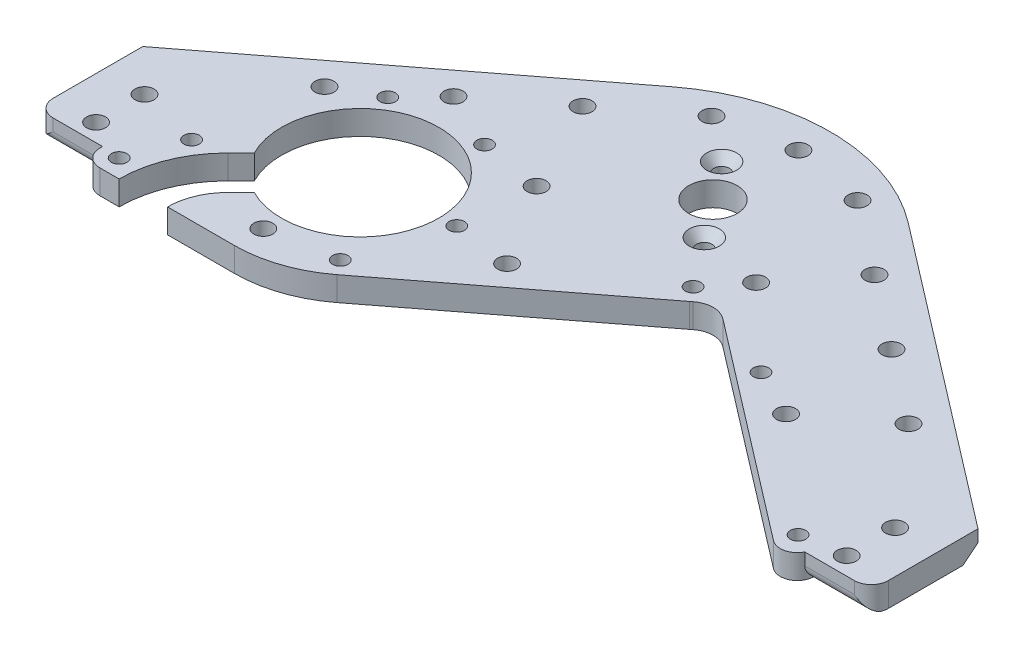
SolidWorks part; units mm, degrees
material "Alum Plate"
ref_plane "Front Plane" through (0, 0, 0) normal (0, 0, 1) x (1, 0, 0)
ref_plane "Top Plane" through (0, 0, 0) normal (0, 1, 0) x (1, 0, 0)
ref_plane "Right Plane" through (0, 0, 0) normal (1, 0, 0) x (0, 0, -1)
sketch "Top Layout" plane through (0, 0, 0) normal (0, 1, 0) x (1, 0, 0)
  line L0 (-114.046, -123.825) -> (-104.775, -123.825) construction
  line L1 (-104.775, -142.875) -> (-101.6, -142.875)
  line L2 (-104.775, -142.875) -> (-104.775, -104.775)
  line L3 (-104.775, -104.775) -> (-101.6, -104.775)
  line L4 (-101.6, -142.875) -> (-101.6, -104.775)
  line L5 (-104.775, -142.875) -> (-101.6, -104.775) construction
  line L6 (-104.775, -104.775) -> (-101.6, -142.875) construction
  line L7 (-19.05, -105.8164) -> (-101.6, -105.8164)
  line L8 (-19.05, -105.8164) -> (-19.05, -141.8336)
  line L9 (-19.05, -141.8336) -> (-101.6, -141.8336)
  line L10 (-101.6, -105.8164) -> (-101.6, -141.8336)
  line L11 (-19.05, -105.8164) -> (-101.6, -141.8336) construction
  line L12 (-19.05, -141.8336) -> (-101.6, -105.8164) construction
  line L13 (-133.096, -85.725) -> (-114.046, -85.725)
  line L14 (-133.096, -85.725) -> (-133.096, -161.925)
  line L15 (-133.096, -161.925) -> (-114.046, -161.925)
  line L16 (-114.046, -85.725) -> (-114.046, -161.925)
  line L17 (-133.096, -85.725) -> (-114.046, -161.925) construction
  line L18 (-133.096, -161.925) -> (-114.046, -85.725) construction
  line L19 (-104.775, -123.825) -> (0, -123.825) construction
  line L20 (0, -123.825) -> (0, 0) construction
  line L21 (-52.3528, -40.1717) -> (0, 0) construction
  line L22 (-70.6449, -16.3328) -> (-18.2922, 23.8388)
  line L23 (-34.0606, -64.0105) -> (18.2922, -23.8388)
  line L24 (-30.9251, 40.3023) -> (-122.2248, -29.7544)
  line L25 (-153.9748, -53.975) -> (-153.9748, -123.825)
  line L26 (-109.5248, -162.052) -> (109.5248, -162.052)
  line L27 (0, -162.052) -> (0, -123.825) construction
  line L28 (-109.5248, -162.052) -> (-109.5248, -20.0093) construction
  line L29 (-104.775, -142.875) -> (-104.775, -152.527)
  line L30 (-104.775, -152.527) -> (104.775, -152.527)
  line L31 (104.775, -104.775) -> (101.6, -104.775)
  line L32 (-144.4498, -73.025) -> (-109.5248, -73.025)
  line L33 (-144.4498, -73.025) -> (-144.4498, -123.825)
  line L34 (-144.4498, -123.825) -> (-109.5248, -123.825) construction
  line L35 (-109.5248, -73.025) -> (-109.5248, -162.052)
  line L36 (-144.4498, -73.025) -> (-109.5248, -123.825) construction
  line L37 (-144.4498, -123.825) -> (-109.5248, -73.025) construction
  line L38 (101.6, -142.875) -> (101.6, -104.775)
  line L39 (104.775, -142.875) -> (101.6, -142.875)
  line L40 (104.775, -142.875) -> (104.775, -104.775)
  line L41 (104.775, -142.875) -> (104.775, -152.527)
  line L42 (109.5248, -162.052) -> (109.5248, -20.0093) construction
  line L43 (30.9251, 40.3023) -> (122.2248, -29.7544)
  line L45 (19.05, -141.8336) -> (101.6, -141.8336)
  line L46 (101.6, -105.8164) -> (101.6, -141.8336)
  line L47 (19.05, -105.8164) -> (101.6, -105.8164)
  line L48 (19.05, -105.8164) -> (19.05, -141.8336)
  line L49 (133.096, -161.925) -> (114.046, -161.925)
  line L50 (114.046, -85.725) -> (114.046, -161.925)
  line L51 (133.096, -85.725) -> (114.046, -85.725)
  line L52 (133.096, -85.725) -> (133.096, -161.925)
  line L53 (144.4498, -123.825) -> (109.5248, -123.825) construction
  line L54 (109.5248, -73.025) -> (109.5248, -162.052)
  line L55 (144.4498, -73.025) -> (109.5248, -73.025)
  line L56 (144.4498, -73.025) -> (144.4498, -123.825)
  line L57 (-109.5248, -123.825) -> (-109.5248, -162.052) construction
  line L62 (-153.9748, -53.975) -> (-122.2248, -53.975)
  line L63 (-122.2248, -53.975) -> (-122.2248, -29.7544)
  line L64 (-144.4498, -123.825) -> (-153.9748, -123.825)
  line L65 (153.9748, -53.975) -> (153.9748, -123.825)
  line L66 (109.5248, -123.825) -> (109.5248, -162.052) construction
  line L67 (144.4498, -123.825) -> (153.9748, -123.825)
  line L68 (122.2248, -29.7544) -> (122.2248, -53.975)
  line L73 (-104.775, -104.775) -> (-104.775, -16.3647) construction
  line L74 (-95.25, -162.052) -> (-95.25, -9.0559) construction
  line L75 (-109.5248, -162.052) -> (-109.5248, -123.825) construction
  line L76 (109.5248, -162.052) -> (109.5248, -123.825) construction
  line L77 (122.2248, -53.975) -> (153.9748, -53.975)
  line L83 (104.775, -155.5496) -> (-104.775, -155.5496) construction
  line L88 (95.25, -162.052) -> (95.25, -9.0559) construction
  line L89 (104.775, -104.775) -> (104.775, -16.3647) construction
  line L92 (-104.775, -152.527) -> (-104.775, -162.052) construction
  line L93 (-14.605, -76.327) -> (14.605, -76.327)
  line L94 (-14.605, -76.327) -> (-14.605, -152.527)
  line L95 (-14.605, -152.527) -> (14.605, -152.527)
  line L96 (14.605, -76.327) -> (14.605, -152.527)
  line L97 (-14.605, -76.327) -> (14.605, -152.527) construction
  line L98 (-14.605, -152.527) -> (14.605, -76.327) construction
  line L99 (104.775, -152.527) -> (104.775, -162.052) construction
  line L100 (-19.05, -105.8164) -> (0, -105.8164) construction
  line L107 (0, -105.8164) -> (19.05, -105.8164) construction
  line L108 (104.775, -123.825) -> (114.046, -123.825) construction
  circle A0 centre (0, 0) radius 114.3
  circle A1 centre (0, 0) radius 6.35
  circle A2 centre (-52.3528, -40.1717) radius 17.8
  circle A3 centre (0, 0) radius 30.0482
  circle A4 centre (-52.3528, -40.1717) radius 30.0482
  arc A5 (-30.9251, 40.3023) -> (30.9251, 40.3023) centre (0, 0) cw
  point P2 (-103.1875, -123.825)
  point P7 (-60.325, -123.825)
  point P12 (-123.571, -123.825)
  point P30 (-126.9873, -98.425)
  point P35 (0, -114.427)
  point P53 (0, -152.527)
  dimension "D1" = 35.6
  dimension "D2" = 12.7
  dimension "D3" = 228.6
  dimension "D11" = 60.0964
  dimension "D12" = 50.8
  dimension "D14" = 52.5
  dimension "D4" = 3.175
  dimension "D5" = 19.05
  dimension "D6" = 76.2
  dimension "D7" = 82.55
  dimension "D8" = 38.1
  dimension "D9" = 104.775
  dimension "D10" = 18.0086
  dimension "D13" = 9.525
  dimension "D15" = 4.7498
  dimension "D16" = 9.525
  dimension "D17" = 9.652
  dimension "D18" = 50.8
  dimension "D19" = 12.446
  dimension "D20" = 65.9892
  dimension "D21" = 19.05
  dimension "D22" = 34.925
  dimension "D23" = 123.825
  dimension "D24" = 12.7
  dimension "D25" = 9.525
  dimension "D26" = 29.21
  dimension "D27" = 76.2
  dimension "D28" = 3.0226
sketch "Side Layout" plane through (0, 0, 0) normal (1, 0, 0) x (0, 0, -1)
  line L0 (0, -38.1) -> (0, 33.7344) construction
  line L1 (-114.3, -20.955) -> (114.3, -20.955)
  line L2 (-114.3, -20.955) -> (-114.3, -33.655)
  line L3 (-114.3, -33.655) -> (114.3, -33.655)
  line L4 (114.3, -20.955) -> (114.3, -33.655)
  line L5 (-114.3, -20.955) -> (114.3, -33.655) construction
  line L6 (-114.3, -33.655) -> (114.3, -20.955) construction
  line L7 (-9.525, -32.9406) -> (9.525, -32.9406)
  line L8 (-9.525, -32.9406) -> (-9.525, -38.1)
  line L9 (-9.525, -38.1) -> (9.525, -38.1)
  line L10 (9.525, -32.9406) -> (9.525, -38.1)
  line L11 (-9.525, -32.9406) -> (9.525, -38.1) construction
  line L12 (-9.525, -38.1) -> (9.525, -32.9406) construction
  line L13 (-11.9126, -29.3338) -> (11.9126, -29.3338)
  line L14 (-11.9126, -29.3338) -> (-11.9126, -32.9406)
  line L15 (-11.9126, -32.9406) -> (11.9126, -32.9406)
  line L16 (11.9126, -29.3338) -> (11.9126, -32.9406)
  line L17 (-11.9126, -29.3338) -> (11.9126, -32.9406) construction
  line L18 (-11.9126, -32.9406) -> (11.9126, -29.3338) construction
  line L19 (-6.35, -32.9406) -> (6.35, -32.9406)
  line L20 (-6.35, -32.9406) -> (-6.35, 33.7344)
  line L21 (-6.35, 33.7344) -> (6.35, 33.7344)
  line L22 (6.35, -32.9406) -> (6.35, 33.7344)
  line L23 (-6.35, -32.9406) -> (6.35, 33.7344) construction
  line L24 (-6.35, 33.7344) -> (6.35, -32.9406) construction
  line L25 (-162.052, 0) -> (-123.825, 0) construction
  line L26 (114.3, -33.655) -> (114.3, 0) construction
  line L27 (-142.875, 19.05) -> (-104.775, 19.05)
  line L28 (-40.1717, -9.525) -> (-40.1717, 5.4) construction
  line L29 (-142.875, 19.05) -> (-142.875, -19.05)
  line L30 (-142.875, -19.05) -> (-104.775, -19.05)
  line L31 (-104.775, 19.05) -> (-104.775, -19.05)
  line L32 (-142.875, 19.05) -> (-104.775, -19.05) construction
  line L33 (-142.875, -19.05) -> (-104.775, 19.05) construction
  line L34 (-130.175, -38.1) -> (-117.9516, -38.1) construction
  line L35 (-57.9717, -14.6) -> (-22.3717, -14.6)
  line L36 (-30.0482, -2.794) -> (30.0482, -2.794)
  line L37 (-30.0482, -2.794) -> (-30.0482, -20.955)
  line L38 (-30.0482, -20.955) -> (30.0482, -20.955)
  line L39 (30.0482, -2.794) -> (30.0482, -20.955)
  line L40 (-30.0482, -2.794) -> (30.0482, -20.955) construction
  line L41 (-30.0482, -20.955) -> (30.0482, -2.794) construction
  line L42 (-30.0482, -2.794) -> (-30.0482, 0) construction
  line L43 (-123.825, 0) -> (0, 0) construction
  line L44 (-57.9717, -14.6) -> (-57.9717, 25.4)
  line L45 (-57.9717, 25.4) -> (-22.3717, 25.4)
  line L46 (-22.3717, -14.6) -> (-22.3717, 25.4)
  line L47 (-19.05, 0) -> (19.05, 0)
  line L48 (-19.05, 0) -> (-19.05, -1.9812)
  line L49 (-19.05, -1.9812) -> (19.05, -1.9812)
  line L50 (19.05, 0) -> (19.05, -1.9812)
  line L51 (-19.05, 0) -> (19.05, -1.9812) construction
  line L52 (-19.05, -1.9812) -> (19.05, 0) construction
  line L53 (-70.2199, -3.175) -> (-10.1235, -3.175)
  line L54 (-70.2199, -3.175) -> (-70.2199, -15.875)
  line L55 (-70.2199, -15.875) -> (-10.1235, -15.875)
  line L56 (-10.1235, -3.175) -> (-10.1235, -15.875)
  line L57 (-70.2199, -3.175) -> (-10.1235, -15.875) construction
  line L58 (-70.2199, -15.875) -> (-10.1235, -3.175) construction
  line L59 (-40.1717, -9.525) -> (-40.1717, 0) construction
  line L60 (-57.9717, -14.6) -> (-22.3717, 25.4) construction
  line L61 (-57.9717, 25.4) -> (-22.3717, -14.6) construction
  line L62 (-22.3717, 0) -> (-57.9717, 0) construction
  line L63 (-137.8162, 0) -> (-123.825, -13.9912) construction
  line L64 (-139.065, 15.24) -> (-108.585, 15.24) construction
  line L65 (-139.065, 15.24) -> (-139.065, -15.24) construction
  line L66 (-139.065, -15.24) -> (-108.585, -15.24) construction
  line L67 (-108.585, 15.24) -> (-108.585, -15.24) construction
  line L68 (-139.065, 15.24) -> (-108.585, -15.24) construction
  line L69 (-139.065, -15.24) -> (-108.585, 15.24) construction
  line L70 (-137.8162, 0) -> (-123.825, 13.9912) construction
  line L71 (-123.825, -13.9912) -> (-109.8338, 0) construction
  line L72 (-123.825, 13.9912) -> (-109.8338, 0) construction
  line L73 (-137.8162, 0) -> (-109.8338, 0) construction
  line L74 (-123.825, -13.9912) -> (-123.825, 13.9912) construction
  line L75 (-6.35, 17.8594) -> (6.35, 17.8594)
  line L76 (114.3, 0) -> (-114.3, 0) construction
  line L77 (-22.3717, 19.05) -> (-6.35, 19.05) construction
  line L78 (-123.825, 38.1) -> (-97.9206, 38.1) construction
  line L79 (-19.05, -3.5814) -> (19.05, -3.5814)
  line L80 (-19.05, -3.5814) -> (-19.05, -1.9812)
  line L81 (-19.05, -1.9812) -> (19.05, -1.9812)
  line L82 (19.05, -3.5814) -> (19.05, -1.9812)
  line L83 (-19.05, -3.5814) -> (19.05, -1.9812) construction
  line L84 (-19.05, -1.9812) -> (19.05, -3.5814) construction
  line L85 (-8.7376, -16.7608) -> (8.7376, -16.7608)
  line L86 (-8.7376, -16.7608) -> (-8.7376, -29.3338)
  line L87 (-8.7376, -29.3338) -> (8.7376, -29.3338)
  line L88 (8.7376, -16.7608) -> (8.7376, -29.3338)
  line L89 (-8.7376, -16.7608) -> (8.7376, -29.3338) construction
  line L90 (-8.7376, -29.3338) -> (8.7376, -16.7608) construction
  line L91 (-8.7376, -3.5814) -> (8.7376, -3.5814)
  line L92 (-8.7376, -3.5814) -> (-8.7376, -16.1544)
  line L93 (-8.7376, -16.1544) -> (8.7376, -16.1544)
  line L94 (8.7376, -3.5814) -> (8.7376, -16.1544)
  line L95 (-8.7376, -3.5814) -> (8.7376, -16.1544) construction
  line L96 (-8.7376, -16.1544) -> (8.7376, -3.5814) construction
  circle A0 centre (-123.825, 0) radius 18.0086
  circle A1 centre (-123.825, 0) radius 38.1
  circle A2 centre (-139.065, 15.24) radius 1.905
  circle A3 centre (-108.585, 15.24) radius 1.905
  circle A4 centre (-108.585, -15.24) radius 1.905
  circle A5 centre (-139.065, -15.24) radius 1.905
  circle A6 centre (-137.8162, 0) radius 1.6002
  circle A7 centre (-123.825, 13.9912) radius 1.6002
  circle A8 centre (-109.8338, 0) radius 1.6002
  circle A9 centre (-123.825, -13.9912) radius 1.6002
  point P0 (0, -27.305)
  point P6 (0, -31.1372)
  point P7 (0, -35.5203)
  point P21 (0, 0.3969)
  point P32 (0, -11.8745)
  point P43 (0, -0.9906)
  point P55 (-40.1717, -9.525)
  point P72 (-40.1717, 5.4)
  point P88 (0, -23.0473)
  point P93 (0, -2.7813)
  point P102 (0, -9.8679)
  dimension "D17" = 3.81
  dimension "D18" = 3.2004
  dimension "D1" = 12.7
  dimension "D2" = 5.1594
  dimension "D3" = 19.05
  dimension "D4" = 3.6068
  dimension "D5" = 23.8252
  dimension "D6" = 12.7
  dimension "D7" = 18.161
  dimension "D8" = 1.9812
  dimension "D9" = 12.7
  dimension "D10" = 40
  dimension "D11" = 25.4
  dimension "D12" = 50.8
  dimension "D13" = 41.275
  dimension "D14" = 30.48
  dimension "D15" = 4.445
  dimension "D16" = 19.7866
  dimension "D19" = 15.875
  dimension "D20" = 6.35
  dimension "D21" = 38.1
  dimension "D22" = 1.6002
  dimension "D23" = 38.1
  dimension "D24" = 17.4752
  dimension "D25" = 12.573
ref_plane "Plane1" through (0, 25.4, 0) normal (0, 1, 0) x (1, 0, 0)
sketch "Sketch3" plane through (0, 25.4, 0) normal (0, 1, 0) x (1, 0, 0)
  line L0 (-104.775, -36.3747) -> (-30.9251, 20.2924)
  line L1 (-104.775, -104.775) -> (-104.775, -16.3647) construction
  line L2 (0, -200130.175) -> (0, 199882.0484) construction
  line L3 (-30.9251, 40.3023) -> (-122.2248, -29.7544) construction
  line L5 (-104.775, -36.3747) -> (-104.775, -77.6497)
  line L6 (-92.075, -77.6497) -> (-104.775, -77.6497)
  line L7 (30.9251, 20.2924) -> (104.775, -36.3747)
  line L8 (104.775, -77.6497) -> (92.075, -77.6497)
  line L9 (104.775, -36.3747) -> (104.775, -77.6497)
  line L11 (104.775, -104.775) -> (104.775, -16.3647) construction
  line L12 (30.9251, 40.3023) -> (122.2248, -29.7544) construction
  line L13 (92.075, -74.6536) -> (24.1423, -22.5271)
  line L14 (-32.2514, -66.3682) -> (20.1013, -26.1965)
  line L15 (-30.9251, 20.2924) -> (0, 44.022)
  line L16 (0, 44.022) -> (30.9251, 20.2924)
  line L17 (-92.075, -77.6497) -> (-92.075, -73.1917)
  line L19 (-92.075, -73.1917) -> (-52.3528, -73.1917)
  line L20 (92.075, -74.6536) -> (92.075, -77.6497)
  circle A1 centre (-52.3528, -40.1717) radius 20.6375
  circle A2 centre (0, 0) radius 6.35
  circle A3 centre (0, 0) radius 6.35 construction
  arc A4 (-52.3528, -73.1917) -> (-32.2514, -66.3682) centre (-52.3528, -40.1717) ccw
  arc A5 (20.1013, -26.1965) -> (24.1423, -22.5271) centre (0, 0) ccw
  arc A6 (30.9251, 20.2924) -> (-30.9251, 20.2924) centre (0, -20.01) ccw construction
  point P28 (0, 44.022)
  dimension "D1" = 33.02
  dimension "D5" = 50.8
  dimension "D7" = 41.275
  dimension "D2" = 41.275
  dimension "D3" = 34.925
  dimension "D4" = 12.7
  dimension "D6" = 38.1
extrude "Boss-Extrude1" add sketch "Sketch3" against normal blind 6.35
ref_plane "Plane3" through (-104.775, 0, 0) normal (-1, 0, 0) x (0, 0, 1)
sketch "Sketch6" plane through (-104.775, 0, 0) normal (-1, 0, 0) x (0, 0, 1)
  line L0 (162.052, -25.4) -> (162.052, 25.4)
  line L1 (162.052, 25.4) -> (77.6497, 25.4)
  line L2 (36.3747, 25.4) -> (77.6497, 25.4) construction
  line L3 (147.7645, 11.1125) -> (162.052, 11.1125) construction
  line L4 (162.052, 0) -> (71.2997, 0) construction
  line L5 (77.6497, 25.4) -> (77.6497, 19.05)
  line L6 (77.6497, 19.05) -> (36.3747, 19.05)
  line L7 (36.3747, 19.05) -> (36.3747, 6.35)
  line L8 (36.3747, 6.35) -> (71.2997, 6.35)
  line L10 (99.6315, -3.175) -> (99.6315, 11.1125) construction
  line L11 (71.2997, -25.4) -> (162.052, -25.4)
  line L13 (71.2997, 6.35) -> (71.2997, -25.4)
  line L14 (152.527, -25.4) -> (152.527, 25.4) construction
  line L15 (99.6315, 11.1125) -> (99.6315, 25.4) construction
  line L16 (147.7645, 11.1125) -> (147.7645, 25.4) construction
  line L17 (94.869, -7.9375) -> (104.394, -7.9375) construction
  line L18 (94.869, -7.9375) -> (94.869, 25.4) construction
  line L19 (94.869, 25.4) -> (104.394, 25.4) construction
  line L20 (104.394, -7.9375) -> (104.394, 25.4) construction
  line L21 (94.869, -7.9375) -> (104.394, 25.4) construction
  line L22 (94.869, 25.4) -> (104.394, -7.9375) construction
  line L23 (147.7645, 11.1125) -> (147.7645, -3.175) construction
  line L24 (104.394, -7.9375) -> (123.825, -7.9375) construction
  line L25 (143.002, -7.9375) -> (152.527, -7.9375) construction
  line L26 (143.002, -7.9375) -> (143.002, 25.4) construction
  line L27 (143.002, 25.4) -> (152.527, 25.4) construction
  line L28 (152.527, -7.9375) -> (152.527, 25.4) construction
  line L29 (143.002, -7.9375) -> (152.527, 25.4) construction
  line L30 (143.002, 25.4) -> (152.527, -7.9375) construction
  line L31 (123.825, -7.9375) -> (152.527, -7.9375) construction
  line L32 (104.775, 19.05) -> (104.775, -19.05) construction
  line L34 (155.702, -25.4) -> (155.702, 25.4) construction
  circle A0 centre (109.8338, 0) radius 1.6002 construction
  circle A1 centre (123.825, 13.9912) radius 1.6002 construction
  circle A2 centre (137.8162, 0) radius 1.6002 construction
  circle A3 centre (123.825, -13.9912) radius 1.6002 construction
  circle A4 centre (109.8338, 0) radius 1.6002 construction
  circle A5 centre (123.825, 13.9912) radius 1.6002 construction
  circle A6 centre (137.8162, 0) radius 1.6002 construction
  circle A7 centre (123.825, -13.9912) radius 1.6002 construction
  circle A8 centre (123.825, 0) radius 18.0086 construction
  circle A9 centre (123.825, 0) radius 18.0086 construction
  circle A10 centre (123.825, 0) radius 9.525
  circle A11 centre (108.585, -15.24) radius 1.905 construction
  circle A12 centre (108.585, 15.24) radius 1.905 construction
  circle A13 centre (139.065, 15.24) radius 1.905 construction
  circle A14 centre (139.065, -15.24) radius 1.905 construction
  circle A15 centre (108.585, -15.24) radius 1.905
  circle A16 centre (108.585, 15.24) radius 1.905
  circle A17 centre (139.065, 15.24) radius 1.905
  circle A18 centre (139.065, -15.24) radius 1.905
  circle A19 centre (147.7645, 11.1125) radius 2.5527
  circle A26 centre (99.6315, 11.1125) radius 2.5527
  circle A27 centre (99.6315, -3.175) radius 2.5527
  circle A28 centre (147.7645, -3.175) radius 2.5527
  point P29 (0, 0)
  point P55 (99.6315, 8.7312)
  point P61 (147.7645, 8.7312)
  dimension "D4" = 19.05
  dimension "D7" = 5.1054
  dimension "D1" = 6.35
  dimension "D2" = 12.7
  dimension "D3" = 25.4
  dimension "D5" = 6.35
  dimension "D6" = 3.175
  dimension "D8" = 0.381
  dimension "D9" = 14.2875
  dimension "D10" = 9.525
  dimension "D12" = 33.3375
sketch "Sketch12" [suppressed] plane through (0, 19.05, 0) normal (0, 1, 0) x (1, 0, 0)
  line L0 (-104.775, -77.6497) -> (-104.775, -36.3747)
  line L1 (-104.775, -36.3747) -> (-92.075, -36.3747)
  line L3 (-92.075, -36.3747) -> (-92.075, -77.6497)
  line L5 (-92.075, -77.6497) -> (-104.775, -77.6497)
  line L6 (-98.425, -77.6497) -> (-98.425, -63.3622) construction
  line L7 (-98.425, -63.3622) -> (-98.425, -50.6622) construction
  line L8 (-98.425, -50.6622) -> (-98.425, -36.3747) construction
  line L10 (-98.425, -36.3747) -> (-104.775, -36.3747) construction
  circle A0 centre (-98.425, -63.3622) radius 2.5527
  circle A1 centre (-98.425, -50.6622) radius 2.5527
  dimension "D2" = 5.1054
  dimension "D1" = 12.7
  dimension "D3" = 12.7
sketch "Sketch8" plane through (0, 25.4, 0) normal (0, 1, 0) x (1, 0, 0)
  line L0 (-109.5248, -162.052) -> (-109.5248, -20.0093) construction
  line L1 (-104.775, -77.6497) -> (-109.5248, -77.6497)
  line L2 (-104.775, -77.6497) -> (-104.775, -36.3747)
  line L3 (-104.775, -36.3747) -> (-109.5248, -36.3747)
  line L4 (-109.5248, -77.6497) -> (-109.5248, -36.3747)
  line L5 (-104.775, -77.6497) -> (-109.5248, -36.3747) construction
  line L6 (-104.775, -36.3747) -> (-109.5248, -77.6497) construction
  line L7 (104.775, -77.6497) -> (109.5248, -77.6497)
  line L8 (104.775, -77.6497) -> (104.775, -36.3747)
  line L9 (104.775, -36.3747) -> (109.5248, -36.3747)
  line L10 (109.5248, -77.6497) -> (109.5248, -36.3747)
  line L11 (104.775, -77.6497) -> (109.5248, -36.3747) construction
  line L12 (104.775, -36.3747) -> (109.5248, -77.6497) construction
  point P4 (-107.1499, -57.0122)
  point P10 (107.1499, -57.0122)
extrude "Boss-Extrude4" add sketch "Sketch8" against normal through all
sketch "Sketch9" plane through (0, 25.4, 0) normal (0, 1, 0) x (1, 0, 0)
  line L0 (7.4916, -9.7632) -> (0, 0) construction
  line L1 (0, 0) -> (-7.4916, 9.7632) construction
  line L2 (0, 44.022) -> (-104.775, -36.3747) construction
  circle A0 centre (-7.4916, 9.7632) radius 2.032
  circle A1 centre (7.4916, -9.7632) radius 2.032
  dimension "D2" = 4.064
  dimension "D1" = 24.6126
extrude "Collar Holes" cut sketch "Sketch9" against normal through all
sketch "Sketch10" plane through (0, 25.4, 0) normal (0, 1, 0) x (1, 0, 0)
  line L0 (0, 33.4567) -> (0, 30.79) construction
  line L1 (-5.1026, 40.1066) -> (0, 33.4567) construction
  line L2 (0, 33.4567) -> (5.1026, 40.1066) construction
  line L3 (0, 44.022) -> (-104.775, -36.3747) construction
  line L4 (104.775, -36.3747) -> (0, 44.022) construction
  circle A0 centre (0, 33.4567) radius 4.7625 construction
  circle A1 centre (0, 33.4567) radius 2.0193
  arc A3 (30.9251, 20.2924) -> (-30.9251, 20.2924) centre (0, -20.01) ccw construction
  dimension "D2" = 9.525
  dimension "D3" = 4.0386
  dimension "D1" = 8.382
extrude "Spacer Holes" cut sketch "Sketch10" against normal through all
pattern_linear "Spacer Hole Pattern" count 5 spacing 24.13 along (-0.7934, 0, 0.6088) of "Spacer Holes"
mirror "Spacer Hole Mirror" about plane through (0, 0, 0) normal (1, 0, 0) of "Spacer Hole Pattern"
sketch "Sketch16" plane through (0, 25.4, 0) normal (0, 1, 0) x (1, 0, 0)
  line L0 (-109.5248, -50.6622) -> (-98.425, -50.6622) construction
  line L1 (-109.5248, -36.3747) -> (-109.5248, -77.6497) construction
  line L2 (-98.425, -50.6622) -> (-98.425, -63.3622) construction
  line L3 (-98.425, -63.3622) -> (-109.5248, -63.3622) construction
  line L4 (-98.425, -63.3622) -> (-98.425, -77.6497) construction
  line L5 (-109.5248, -77.6497) -> (-92.075, -77.6497) construction
  line L6 (-98.425, -50.6622) -> (-98.425, -36.3747) construction
  line L7 (-104.775, -36.3747) -> (-109.5248, -36.3747) construction
  line L8 (-104.775, -36.3747) -> (-104.775, -77.6497) construction
  line L9 (0, 0) -> (0, 30.79) construction
  line L10 (104.775, -36.3747) -> (104.775, -77.6497) construction
  circle A0 centre (-98.425, -50.6622) radius 2.0193
  circle A1 centre (-98.425, -63.3622) radius 2.0193
  circle A4 centre (98.425, -63.3622) radius 2.0193
  circle A5 centre (98.425, -50.6622) radius 2.0193
  arc A6 (30.9251, 20.2924) -> (-30.9251, 20.2924) centre (0, -20.01) ccw construction
  dimension "D1" = 4.0386
  dimension "D2" = 12.7
  dimension "D3" = 6.35
extrude "Custom Nutstrip Holes" cut sketch "Sketch16" against normal through all
sketch "Sketch36" plane through (0, 25.4, 0) normal (0, 1, 0) x (1, 0, 0)
  line L0 (-52.3528, -65.5717) -> (-12.44, -41.5615) construction
  line L1 (-12.44, -41.5615) -> (24.5129, -13.2066) construction
  line L2 (24.5129, -13.2066) -> (58.2939, -39.1277) construction
  line L3 (-32.2514, -66.3682) -> (20.1013, -26.1965) construction
  line L4 (24.1423, -22.5271) -> (92.075, -74.6536) construction
  line L5 (-12.44, -41.5615) -> (-7.8012, -47.6069) construction
  line L6 (58.2939, -39.1277) -> (53.6552, -45.1731) construction
  line L7 (-52.3528, -65.5717) -> (-52.3528, -40.1717) construction
  line L8 (58.2939, -39.1277) -> (92.075, -65.0488) construction
  line L9 (92.075, -65.0488) -> (92.075, -77.6497) construction
  line L10 (-52.3528, -40.1717) -> (-26.1764, -20.0858) construction
  line L11 (-26.1764, -20.0858) -> (0, 0) construction
  line L12 (92.075, -74.6536) -> (92.075, -77.6497) construction
  circle A0 centre (-52.3528, -65.5717) radius 2.0193
  circle A1 centre (58.2939, -39.1277) radius 2.0193
  circle A2 centre (24.5129, -13.2066) radius 2.0193
  circle A3 centre (-12.44, -41.5615) radius 2.0193
  circle A4 centre (-76.5745, -25.3009) radius 2.0193 construction
  circle A5 centre (-52.3528, -65.5717) radius 4.7625 construction
  circle A6 centre (-12.44, -41.5615) radius 4.7625 construction
  circle A7 centre (24.5129, -13.2066) radius 4.7625 construction
  circle A8 centre (58.2939, -39.1277) radius 4.7625 construction
  arc A9 (-52.3528, -73.1917) -> (-32.2514, -66.3682) centre (-52.3528, -40.1717) ccw construction
  circle A10 centre (-26.1764, -20.0858) radius 2.0193
  dimension "D1" = 9.525
  dimension "D2" = 25.4
  dimension "D3" = 7.62
extrude "Aux Spacer Holes" cut sketch "Sketch36" against normal through all
sketch "Sketch38" [suppressed] plane through (-104.775, 0, 0) normal (-1, 0, 0) x (0, 0, 1)
  line L1 (152.527, -7.9375) -> (143.002, -7.9375)
  line L2 (152.527, -7.9375) -> (152.527, 25.4)
  line L3 (152.527, 25.4) -> (143.002, 25.4)
  line L4 (143.002, -7.9375) -> (143.002, 25.4)
  line L5 (152.527, -7.9375) -> (143.002, 25.4) construction
  line L6 (152.527, 25.4) -> (143.002, -7.9375) construction
  point P4 (147.7645, 8.7312)
extrude "Cut-Extrude16" [suppressed] cut sketch "Sketch38" against normal blind 9.525
sketch "Sketch46" [suppressed] plane through (-104.775, 0, 0) normal (-1, 0, 0) x (0, 0, 1)
  line L0 (142.875, 19.05) -> (104.775, -19.05) construction
  line L1 (104.14, 19.685) -> (143.51, 19.685)
  line L2 (104.14, 19.685) -> (104.14, -19.685)
  line L3 (104.14, -19.685) -> (143.51, -19.685)
  line L4 (143.51, 19.685) -> (143.51, -19.685)
  line L5 (104.14, 19.685) -> (143.51, -19.685) construction
  line L6 (104.14, -19.685) -> (143.51, 19.685) construction
  point P0 (123.825, 0)
  dimension "D1" = 39.37
extrude "Cut-Extrude21" [suppressed] cut sketch "Sketch46" against normal blind 6.985
ref_plane "Plane5" through (0, 0, 152.527) normal (0, 0, 1) x (1, 0, 0)
sketch "Sketch41" plane through (0, 0, 152.527) normal (0, 0, 1) x (1, 0, 0)
  line L0 (-104.775, -7.9375) -> (-104.775, 25.4) construction
  line L1 (-104.775, -7.9375) -> (-104.775, 12.7)
  line L2 (-104.775, -7.9375) -> (104.775, -7.9375)
  line L3 (104.775, -7.9375) -> (104.775, 12.7)
  line L4 (104.775, 25.4) -> (-104.775, 25.4)
  line L5 (0, -7.9375) -> (0, 25.4) construction
  line L6 (-104.775, 3.9624) -> (-100.0125, 3.9624) construction
  line L7 (-100.0125, 3.9624) -> (-100.0125, 25.4) construction
  line L8 (104.775, 3.9624) -> (100.0125, 3.9624) construction
  line L9 (100.0125, 3.9624) -> (100.0125, 25.4) construction
  line L10 (19.05, 20.6375) -> (23.8252, 20.6375) construction
  line L11 (19.05, 15.875) -> (78.5876, 15.875) construction
  line L12 (19.05, 15.875) -> (19.05, 25.4) construction
  line L13 (19.05, 25.4) -> (78.5876, 25.4) construction
  line L14 (78.5876, 15.875) -> (78.5876, 25.4) construction
  line L15 (19.05, 15.875) -> (78.5876, 25.4) construction
  line L16 (19.05, 25.4) -> (78.5876, 15.875) construction
  line L17 (23.8252, 20.6375) -> (38.1127, 20.6375) construction
  line L18 (38.1127, 20.6375) -> (52.4002, 20.6375) construction
  line L19 (52.4002, 20.6375) -> (66.6877, 20.6375) construction
  line L20 (-104.775, 25.4) -> (-112.395, 25.4)
  line L21 (-112.395, 25.4) -> (-112.395, 3.175)
  line L22 (-112.395, 3.175) -> (-109.5248, 3.175)
  line L23 (-109.5248, 3.175) -> (-109.5248, 12.7)
  line L24 (-109.5248, 12.7) -> (-104.775, 12.7)
  line L25 (-104.775, 12.7) -> (-104.775, 25.4) construction
  line L26 (104.775, 25.4) -> (112.395, 25.4)
  line L27 (112.395, 25.4) -> (112.395, 3.175)
  line L28 (112.395, 3.175) -> (109.5248, 3.175)
  line L29 (109.5248, 3.175) -> (109.5248, 12.7)
  line L30 (109.5248, 12.7) -> (104.775, 12.7)
  line L31 (104.775, 12.7) -> (104.775, 25.4) construction
  line L32 (-100.0125, 3.9624) -> (-87.3125, 3.9624) construction
  line L33 (-63.5, -1.5875) -> (0, -1.5875) construction
  line L34 (0, -1.5875) -> (63.5, -1.5875) construction
  line L35 (63.5, -1.5875) -> (63.5, -7.9375) construction
  circle A0 centre (-100.0125, 3.9624) radius 2.5527
  circle A1 centre (100.0125, 3.9624) radius 2.5527
  circle A2 centre (23.8252, 20.6375) radius 2.5527
  circle A3 centre (38.1127, 20.6375) radius 2.5527
  circle A4 centre (52.4002, 20.6375) radius 2.5527
  circle A5 centre (66.6877, 20.6375) radius 2.5527
  circle A6 centre (-66.6877, 20.6375) radius 2.5527
  circle A7 centre (-52.4002, 20.6375) radius 2.5527
  circle A8 centre (-38.1127, 20.6375) radius 2.5527
  circle A9 centre (-23.8252, 20.6375) radius 2.5527
  circle A10 centre (-87.3125, 3.9624) radius 2.5527
  circle A11 centre (87.3125, 3.9624) radius 2.5527
  circle A12 centre (-63.5, -1.5875) radius 2.5527
  circle A13 centre (63.5, -1.5875) radius 2.5527
  point P14 (48.8188, 20.6375)
  dimension "D3" = 5.1054
  dimension "D7" = 5.1054
  dimension "D1" = 21.4376
  dimension "D2" = 4.7625
  dimension "D4" = 9.525
  dimension "D5" = 59.5376
  dimension "D6" = 4.7752
  dimension "D8" = 14.2875
  dimension "D9" = 7.62
  dimension "D10" = 4.7498
  dimension "D11" = 12.7
  dimension "D12" = 9.525
  dimension "D13" = 19.05
  dimension "D14" = 12.7
  dimension "D15" = 6.35
  dimension "D16" = 63.5
sketch "Sketch43" [suppressed] plane through (-109.5248, 0, 0) normal (-1, 0, 0) x (0, 0, 1)
  line L1 (152.527, 12.7) -> (155.702, 12.7)
  line L2 (152.527, 12.7) -> (152.527, 25.4)
  line L3 (152.527, 25.4) -> (155.702, 25.4)
  line L4 (155.702, 12.7) -> (155.702, 25.4)
  line L5 (152.527, 12.7) -> (155.702, 25.4) construction
  line L6 (152.527, 25.4) -> (155.702, 12.7) construction
  line L7 (162.052, 25.4) -> (77.6497, 25.4) construction
  point P4 (154.1145, 19.05)
  dimension "D1" = 3.175
sketch "Sketch44" plane through (0, 25.4, 0) normal (0, 1, 0) x (1, 0, 0)
  line L0 (73.8315, -147.7645) -> (73.8315, -152.527) construction
  line L1 (92.075, -74.6536) -> (92.075, -77.6497) construction
  line L2 (-92.075, -77.6497) -> (-92.075, -73.1917) construction
  line L3 (0, -123.825) -> (0, 0) construction
  line L4 (-92.075, -73.1917) -> (-52.3528, -73.1917) construction
  line L5 (-104.775, -104.775) -> (-104.775, -16.3647) construction
  line L6 (-32.2514, -66.3682) -> (20.1013, -26.1965) construction
  line L21 (-104.775, -68.1247) -> (-104.775, -152.527)
  line L22 (-104.775, -152.527) -> (104.775, -152.527)
  line L23 (104.775, -152.527) -> (104.775, -68.1247)
  line L34 (-104.775, -99.6315) -> (-100.0125, -99.6315) construction
  line L35 (-104.775, -147.7645) -> (-100.0125, -147.7645) construction
  line L36 (0, -152.527) -> (0, -35.6178) construction
  line L38 (30.969, -147.7645) -> (45.2565, -147.7645) construction
  line L39 (45.2565, -147.7645) -> (59.544, -147.7645) construction
  line L40 (59.544, -147.7645) -> (73.8315, -147.7645) construction
  line L41 (23.8252, -152.527) -> (30.969, -152.527) construction
  line L42 (104.775, -152.527) -> (-104.775, -152.527) construction
  line L43 (30.969, -152.527) -> (38.1127, -152.527) construction
  line L44 (30.969, -152.527) -> (30.969, -147.7645) construction
  line L45 (-92.075, -77.6497) -> (-104.775, -77.6497) construction
  line L48 (-35.1507, -62.5899) -> (-8.9743, -42.504) construction
  line L49 (-8.9743, -42.504) -> (17.2021, -22.4182) construction
  line L50 (45.5313, -32.9364) -> (87.3125, -64.9962) construction
  line L51 (92.075, -74.6536) -> (24.1423, -22.5271) construction
  line L52 (104.775, -77.6497) -> (92.075, -77.6497) construction
  line L79 (-104.775, -68.1247) -> (-92.075, -68.1247)
  line L80 (-92.075, -68.1247) -> (-92.075, -63.6667)
  line L85 (21.8118, -8.7328) -> (92.075, -62.6476)
  line L86 (-38.0499, -58.8115) -> (14.3028, -18.6398)
  line L87 (-92.075, -63.6667) -> (-52.3528, -63.6667)
  line L88 (92.075, -62.6476) -> (92.075, -68.1247)
  line L89 (92.075, -68.1247) -> (104.775, -68.1247)
  circle A0 centre (-73.8315, -147.7645) radius 2.5527
  circle A1 centre (-59.544, -147.7645) radius 2.5527
  circle A2 centre (-45.2565, -147.7645) radius 2.5527
  circle A3 centre (-30.969, -147.7645) radius 2.5527
  circle A17 centre (-100.0125, -99.6315) radius 2.5527
  circle A18 centre (-100.0125, -147.7645) radius 2.5527
  circle A19 centre (100.0125, -147.7645) radius 2.5527
  circle A20 centre (100.0125, -99.6315) radius 2.5527
  circle A21 centre (30.969, -147.7645) radius 2.5527
  circle A22 centre (45.2565, -147.7645) radius 2.5527
  circle A23 centre (59.544, -147.7645) radius 2.5527
  circle A24 centre (73.8315, -147.7645) radius 2.5527
  circle A25 centre (-87.3125, -68.4292) radius 4.7625 construction
  circle A26 centre (-35.1507, -62.5899) radius 4.7625 construction
  circle A27 centre (-8.9743, -42.504) radius 4.7625 construction
  circle A28 centre (17.2021, -22.4182) radius 4.7625 construction
  circle A29 centre (45.5313, -32.9364) radius 4.7625 construction
  circle A30 centre (87.3125, -64.9962) radius 4.7625 construction
  circle A32 centre (-87.3125, -68.4292) radius 2.5527
  circle A33 centre (-35.1507, -62.5899) radius 2.5527
  circle A34 centre (-8.9743, -42.504) radius 2.5527 construction
  circle A35 centre (17.2021, -22.4182) radius 2.5527
  circle A36 centre (45.5313, -32.9364) radius 2.5527
  circle A37 centre (87.3125, -64.9962) radius 2.5527
  circle A38 centre (-97.155, -85.2697) radius 7.62 construction
  circle A39 centre (97.155, -85.2697) radius 7.62 construction
  circle A40 centre (24.5121, -32.4156) radius 7.62 construction
  arc A41 (20.1013, -26.1965) -> (24.1423, -22.5271) centre (0, 0) ccw construction
  circle A42 centre (-97.155, -85.2697) radius 2.5527
  circle A43 centre (24.5121, -32.4156) radius 2.5527
  circle A44 centre (97.155, -85.2697) radius 2.5527
  arc A56 (14.3028, -18.6398) -> (21.8118, -8.7328) centre (0, 0) ccw
  arc A57 (-52.3528, -63.6667) -> (-38.0499, -58.8115) centre (-52.3528, -40.1717) ccw
  point P4 (-104.775, -152.527)
  dimension "D2" = 5.1054
  dimension "D7" = 5.1054
  dimension "D8" = 15.24
  dimension "D3" = 9.525
  dimension "D9" = 9.525
  dimension "D4" = 4.7625
  dimension "D5" = 14.2875
  dimension "D6" = 9.525
  dimension "D1" = 4.7625
  dimension "D10" = 52.664
sketch "Sketch82" [suppressed] plane through (0, 28.829, 0) normal (0, 1, 0) x (1, 0, 0)
  line L0 (-52.3528, -63.6667) -> (-92.075, -63.6667) construction
  line L1 (-52.3528, -65.5717) -> (-52.3528, -63.6667) construction
  line L2 (-12.4467, -41.5667) -> (-13.6064, -40.0553) construction
  line L3 (14.3028, -18.6398) -> (-38.0499, -58.8115) construction
  line L4 (24.5175, -13.2101) -> (25.6772, -11.6988) construction
  line L5 (92.075, -62.6476) -> (21.8118, -8.7328) construction
  line L6 (58.2962, -39.1295) -> (59.4559, -37.6181) construction
  line L7 (21.4643, -9.5551) -> (21.8118, -8.7328)
  line L8 (21.8118, -8.7328) -> (22.2143, -9.0416)
  circle A0 centre (-52.3528, -65.5717) radius 4.7625
  circle A1 centre (-12.4467, -41.5667) radius 4.7625
  arc A2 (21.4643, -9.5551) -> (22.2143, -9.0416) centre (24.5175, -13.2101) ccw
  circle A3 centre (58.2962, -39.1295) radius 4.7625
  arc A4 (14.3028, -18.6398) -> (21.8118, -8.7328) centre (0, 0) ccw construction
  dimension "D1" = 9.525
  dimension "D2" = 1.905
  dimension "D3" = 30.8104
  dimension "D4" = 83.6926
  dimension "D5" = 41.1154
extrude "Cut-Extrude38" [suppressed] cut sketch "Sketch82" against normal up to surface (3.429 mm away)
sketch "Sketch45" [suppressed] plane through (0, -25.4, 0) normal (0, -1, 0) x (1, 0, 0)
  circle A2 centre (24.5121, 32.4156) radius 6.35
  circle A4 centre (-97.155, 85.2697) radius 6.35
  circle A5 centre (97.155, 85.2697) radius 6.35
  dimension "D1" = 12.7
ref_plane "Plane6" through (0, 19.05, 0) normal (0, 1, 0) x (1, 0, 0)
sketch "Sketch59" [suppressed] plane through (0, 19.05, 0) normal (0, 1, 0) x (1, 0, 0)
  line L0 (0, 22.408) -> (0, 30.79) construction
  line L1 (-19.1436, 18.7673) -> (-24.2463, 25.4172) construction
  line L2 (0, 33.4567) -> (-5.1026, 40.1066) construction
  line L3 (-5.1026, 40.1066) -> (-24.2463, 25.4172) construction
  line L4 (-104.775, -36.3747) -> (-30.9251, 20.2924) construction
  line L5 (-19.1436, 18.7673) -> (0, 33.4567) construction
  circle A0 centre (0, 22.408) radius 4.7625
  circle A2 centre (-19.1436, 18.7673) radius 4.7625
  arc A3 (30.9251, 20.2924) -> (-30.9251, 20.2924) centre (0, -20.01) ccw construction
  dimension "D3" = 9.525
  dimension "D1" = 8.382
  dimension "D2" = 24.13
sketch "Sketch47" plane through (0, 25.4, 0) normal (0, 1, 0) x (1, 0, 0)
  line L0 (-21.3485, -42.7945) -> (-23.7291, -44.6212) construction
  line L1 (-81.9672, -61.1267) -> (-75.3534, -61.1267) construction
  line L2 (-19.1436, 18.7673) -> (-38.2872, 4.0779) construction
  line L3 (-38.2872, 4.0779) -> (-57.4308, -10.6115) construction
  line L4 (-57.4308, -10.6115) -> (-76.5745, -25.3009) construction
  line L5 (-19.1436, 18.7673) -> (0, 33.4567) construction
  line L6 (-76.5745, -25.3009) -> (-65.8758, -19.4248) construction
  line L7 (-65.8758, -19.4248) -> (-57.4308, -10.6115) construction
  line L9 (-87.7466, -52.146) -> (-71.6552, -16.7941)
  line L10 (-38.0499, -58.8115) -> (14.3028, -18.6398) construction
  line L11 (-81.9672, -54.7767) -> (-52.3528, -40.1717) construction
  line L12 (-52.3528, -40.1717) -> (-65.8758, -19.4248) construction
  line L13 (-92.075, -63.6667) -> (-52.3528, -63.6667) construction
  line L14 (-70.5066, -49.3452) -> (-83.977, -62.8156) construction
  line L15 (-23.7291, -44.6212) -> (-39.5962, -56.7964)
  line L16 (-52.3528, -61.1267) -> (-81.9672, -61.1267)
  line L17 (-42.4227, -17.4847) -> (-52.3528, -40.1717) construction
  line L18 (-52.3528, -40.1717) -> (-27.5947, -39.5834) construction
  line L19 (-81.9672, -54.7767) -> (-65.8758, -19.4248) construction
  line L20 (-65.8758, -19.4248) -> (-42.4227, -17.4847) construction
  line L21 (-42.4227, -17.4847) -> (-27.5947, -39.5834) construction
  line L22 (-83.977, -62.8156) -> (-74.9967, -71.7959) construction
  line L23 (-74.9967, -71.7959) -> (-61.5263, -58.3255) construction
  line L24 (-79.4868, -67.3058) -> (-52.3528, -40.1717) construction
  line L25 (-52.3528, -60.5117) -> (-52.3528, -40.1717) construction
  arc A0 (-87.7466, -52.146) -> (-81.9672, -61.1267) centre (-81.9672, -54.7767) ccw
  arc A1 (-23.7291, -44.6212) -> (-27.4458, -33.2351) centre (-27.5947, -39.5834) ccw
  arc A2 (-60.2505, -16.4788) -> (-71.6552, -16.7941) centre (-65.8758, -19.4248) ccw
  arc A3 (-36.4919, -19.7535) -> (-48.4556, -15.5031) centre (-42.4227, -17.4847) ccw
  arc A4 (-21.3485, -42.7945) -> (-75.3534, -61.1267) centre (-52.3528, -40.1717) ccw construction
  arc A5 (-52.3528, -63.6667) -> (-38.0499, -58.8115) centre (-52.3528, -40.1717) ccw construction
  arc A6 (-52.3528, -61.1267) -> (-39.5962, -56.7964) centre (-52.3528, -40.1717) ccw
  circle A7 centre (-81.9672, -54.7767) radius 2.4892
  circle A8 centre (-65.8758, -19.4248) radius 2.4892
  circle A9 centre (-42.4227, -17.4847) radius 2.4892
  circle A10 centre (-27.5947, -39.5834) radius 2.4892
  circle A11 centre (-52.3528, -40.1717) radius 6.985
  arc A13 (-60.2505, -16.4788) -> (-48.4556, -15.5031) centre (-54.5593, -13.4984) ccw
  arc A14 (-36.4919, -19.7535) -> (-27.4458, -33.2351) centre (-27.2129, -23.3031) ccw
  circle A15 centre (-52.3528, -40.1717) radius 20.34 construction
  circle A16 centre (-52.3528, -40.1717) radius 17.8 construction
  dimension "D2" = 62.23
  dimension "D3" = 4.9784
  dimension "D7" = 13.97
  dimension "D8" = 45
  dimension "D10" = 12.7
  dimension "D11" = 2.54
  dimension "D4" = 2.54
  dimension "D5" = 33.02
  dimension "D6" = 6.35
  dimension "D9" = 65
  dimension "D12" = 19.05
sketch "Sketch49" plane through (0, 25.4, 0) normal (0, 1, 0) x (1, 0, 0)
  circle A0 centre (-81.9672, -54.7767) radius 2.0193
  circle A1 centre (-65.8758, -19.4248) radius 2.0193
  circle A2 centre (-42.4227, -17.4847) radius 2.0193
  circle A3 centre (-27.5947, -39.5834) radius 2.0193
  dimension "D1" = 4.0386
extrude "Cut-Extrude23" cut sketch "Sketch49" against normal through all
sketch "Sketch50" plane through (0, 25.4, 0) normal (0, 1, 0) x (1, 0, 0)
  circle A0 centre (-87.3125, -68.4292) radius 2.0193
  circle A1 centre (-35.1507, -62.5899) radius 2.0193
  circle A3 centre (17.2021, -22.4182) radius 2.0193
  circle A4 centre (45.5313, -32.9364) radius 2.0193
  circle A5 centre (87.3125, -64.9962) radius 2.0193
  circle A6 centre (-27.5947, -39.5834) radius 2.0193 construction
extrude "Cut-Extrude24" cut sketch "Sketch50" against normal through all
sketch "Sketch58" plane through (0, 25.4, 0) normal (0, 1, 0) x (1, 0, 0)
  line L0 (0, 22.408) -> (0, 30.79) construction
  line L1 (-30.9251, 20.2924) -> (0, 44.022)
  line L2 (0, 44.022) -> (30.9251, 20.2924)
  circle A0 centre (0, 22.408) radius 2.0193
  arc A1 (30.9251, 20.2924) -> (-30.9251, 20.2924) centre (0, -20.01) ccw construction
  circle A2 centre (19.1436, 18.7673) radius 2.0193 construction
  arc A4 (-30.9251, 20.2924) -> (30.9251, 20.2924) centre (0, -20.01) cw
  dimension "D1" = 8.382
extrude "Cut-Extrude30" cut sketch "Sketch58" against normal through all
sketch "Sketch11" plane through (0, 25.4, 0) normal (0, 1, 0) x (1, 0, 0)
  circle A0 centre (0, 22.408) radius 2.4892
  circle A1 centre (-76.5745, -25.3009) radius 2.4892
  circle A2 centre (-57.4308, -10.6115) radius 2.4892
  circle A3 centre (-38.2872, 4.0779) radius 2.4892
  circle A4 centre (-19.1436, 18.7673) radius 2.4892
  circle A5 centre (19.1436, 18.7673) radius 2.4892
  circle A6 centre (38.2872, 4.0779) radius 2.4892
  circle A7 centre (57.4308, -10.6115) radius 2.4892
  circle A8 centre (76.5745, -25.3009) radius 2.4892
  circle A10 centre (-52.3528, -65.5717) radius 2.4892
  circle A11 centre (-98.425, -50.6622) radius 2.4892
  circle A12 centre (-98.425, -63.3622) radius 2.4892
  circle A13 centre (98.425, -50.6622) radius 2.4892
  circle A14 centre (98.425, -63.3622) radius 2.4892
  circle A16 centre (-26.1764, -20.0858) radius 2.4892
  circle A17 centre (-12.44, -41.5615) radius 2.4892
  circle A18 centre (24.5129, -13.2066) radius 2.4892
  circle A19 centre (58.2939, -39.1277) radius 2.4892
  dimension "D1" = 4.9784
extrude "Enlarge Spacer Holes" cut sketch "Sketch11" against normal through all
chamfer "Top Chamfer" distance 1.905 distance2 2.54 2 edges at (7.4916, 25.4, 11.7952) (-7.4916, 25.4, -7.7312) first distance on face at (-98.425, 25.4, 53.1514)
sketch "Sketch75" plane through (0, 25.4, 0) normal (0, 1, 0) x (1, 0, 0)
  line L0 (-104.775, -36.3747) -> (-109.5248, -40.0193)
  line L1 (-109.5248, -36.3747) -> (-109.5248, -77.6497) construction
  line L2 (-109.5248, -40.0193) -> (-109.5248, -36.3747)
  line L3 (-109.5248, -36.3747) -> (-104.775, -36.3747)
  line L4 (104.775, -36.3747) -> (109.5248, -40.0193)
  line L5 (109.5248, -77.6497) -> (109.5248, -36.3747) construction
  line L6 (109.5248, -40.0193) -> (109.5248, -36.3747)
  line L7 (109.5248, -36.3747) -> (104.775, -36.3747)
  line L8 (104.775, -36.3747) -> (30.9251, 20.2924) construction
  line L9 (-30.9251, 20.2924) -> (-104.775, -36.3747) construction
extrude "Cut-Extrude34" cut sketch "Sketch75" against normal through all
sketch "Sketch101" plane through (0, 25.4, 0) normal (0, 1, 0) x (1, 0, 0)
  line L0 (-61.7476, -58.5468) -> (-65.2238, -62.0229)
  line L1 (-74.9967, -71.7959) -> (-61.5263, -58.3255) construction
  line L2 (-70.7278, -49.5665) -> (-74.204, -53.0427)
  line L3 (-70.5066, -49.3452) -> (-83.977, -62.8156) construction
  line L4 (-76.2, -73.1917) -> (-76.2, -55.2595) construction
  line L5 (-79.4868, -67.3058) -> (-52.3528, -40.1717) construction
  line L6 (-82.55, -73.1917) -> (-69.85, -73.1917)
  line L7 (-92.075, -73.1917) -> (-52.3528, -73.1917) construction
  line L8 (-69.85, -73.1917) -> (-69.85, -50.5429) construction
  line L9 (-70.7278, -49.5665) -> (-61.7476, -58.5468)
  circle A0 centre (-52.3528, -40.1717) radius 20.6375 construction
  arc A1 (-65.2238, -62.0229) -> (-69.85, -73.1917) centre (-54.055, -73.1917) ccw
  arc A2 (-74.204, -53.0427) -> (-82.55, -73.1917) centre (-54.055, -73.1917) ccw
  circle A3 centre (-52.3528, -40.1717) radius 20.34 construction
  dimension "D1" = 76.2
extrude "Cut-Extrude52" cut sketch "Sketch101" against normal through all
sketch "Sketch110" plane through (0, 25.4, 0) normal (0, 1, 0) x (1, 0, 0)
  line L1 (-109.5248, -77.6497) -> (-92.075, -77.6497)
  line L2 (-109.5248, -77.6497) -> (-109.5248, -67.9977)
  line L3 (-109.5248, -67.9977) -> (-92.075, -67.9977)
  line L4 (-92.075, -77.6497) -> (-92.075, -67.9977)
  line L5 (-109.5248, -77.6497) -> (-92.075, -67.9977) construction
  line L6 (-109.5248, -67.9977) -> (-92.075, -77.6497) construction
  line L7 (109.5248, -77.6497) -> (92.075, -77.6497)
  line L8 (109.5248, -77.6497) -> (109.5248, -67.9977)
  line L9 (109.5248, -67.9977) -> (92.075, -67.9977)
  line L10 (92.075, -77.6497) -> (92.075, -67.9977)
  line L11 (109.5248, -77.6497) -> (92.075, -67.9977) construction
  line L12 (109.5248, -67.9977) -> (92.075, -77.6497) construction
  point P4 (-100.7999, -72.8237)
  point P12 (100.7999, -72.8237)
  dimension "D1" = 9.652
extrude "Cut-Extrude56" cut sketch "Sketch110" against normal through all
chamfer "Chamfer4" distance 3.175 3 edges at (70.2249, 19.05, 9.8635) (-70.2249, 19.05, 9.8635) (0, 19.05, -30.79) tangent propagation no
fillet "Fillet21" radius 6.35 1 edges at (24.1423, 22.225, 22.5271)
fillet "Fillet41" radius 4.445 4 edges at (109.5248, 22.225, 67.9977) (92.075, 22.225, 74.6536) (-92.075, 22.225, 73.1917) (-109.5248, 22.225, 67.9977)
fillet "Fillet45" radius 3.175 2 edges at (98.5774, 19.05, 67.9977) (-98.5774, 19.05, 67.9977) tangent propagation no
sketch "Sketch111" plane through (0, 25.4, 0) normal (0, 1, 0) x (1, 0, 0)
  circle A0 centre (7.4916, -9.7632) radius 4.7625 construction
  circle A1 centre (-7.4916, 9.7632) radius 4.7625 construction
  circle A2 centre (0, 0) radius 17.78
  circle A5 centre (0, 0) radius 6.985
  dimension "D1" = 13.97
  dimension "D2" = 9.525
  dimension "D3" = 35.56
